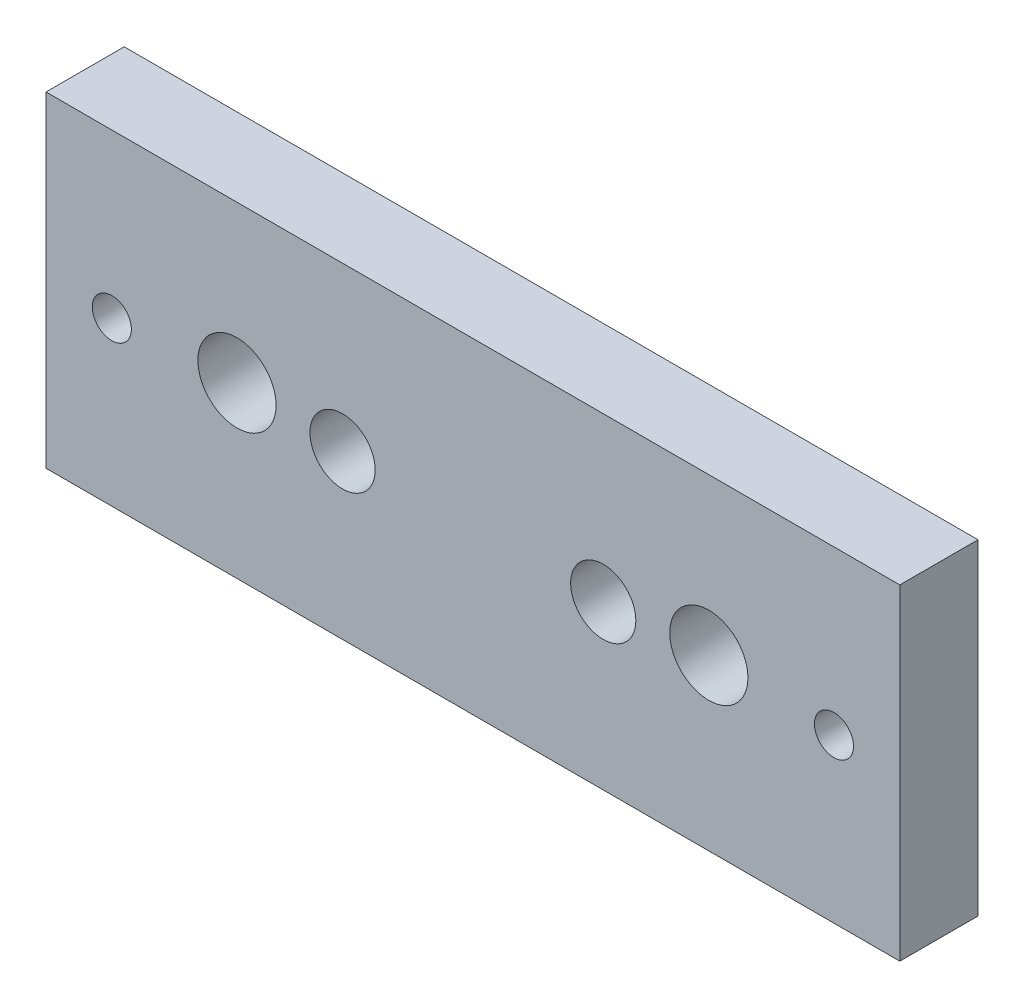
SolidWorks part; units mm, degrees
ref_plane "Płaszczyzna przednia" through (0, 0, 0) normal (0, 0, 1) x (1, 0, 0)
ref_plane "Płaszczyzna górna" through (0, 0, 0) normal (0, 1, 0) x (1, 0, 0)
ref_plane "Płaszczyzna prawa" through (0, 0, 0) normal (1, 0, 0) x (0, 0, -1)
sketch "Sketch1" plane through (0, 0, 0) normal (0, 0, 1) x (1, 0, 0)
  line L1 (0, 0) -> (65.5, 0)
  line L2 (0, 0) -> (0, 25)
  line L3 (0, 25) -> (65.5, 25)
  line L4 (65.5, 0) -> (65.5, 25)
  dimension "D1" = 65.5
  dimension "D2" = 25
extrude "Boss-Extrude1" add sketch "Sketch1" along normal blind 6
hole_wizard "Ø5.0mm Dowel Hole1" positions "Sketch2" profile "Sketch3" hole size "Ø5.0" standard "ANSI Metric" end condition through all
sketch "Sketch2" plane through (0, 0, 6) normal (0, 0, 1) x (1, 0, 0)
  line L0 (0, 0) -> (65.5, 0) construction
  line L1 (0, 25) -> (0, 0) construction
  point P0 (22.75, 12.5)
  point P2 (42.75, 12.5)
  dimension "D1" = 12.5
  dimension "D2" = 22.75
  dimension "D3" = 20
sketch "Sketch3" plane through (22.75, 12.5, 6) normal (1, 0, 0) x (0, -1, 0)
  line L0 (0, 0) -> (0, 6)
  line L1 (0, 6) -> (2.5, 6)
  line L2 (2.5, 6) -> (2.5, 0)
  line L5 (2.5, 0) -> (0, 0)
  line L11 (0, -6.35) -> (0, 107.95) construction
  dimension "Thru Hole Dia." = 5
  dimension "Thru Hole Depth" = 6
sketch "Sketch4" plane through (0, 0, 6) normal (0, 0, 1) x (1, 0, 0)
  line L0 (65.5, 25) -> (0, 25) construction
  line L1 (0, 25) -> (0, 0) construction
  circle A0 centre (14.65, 13) radius 3
  circle A1 centre (50.85, 13) radius 3
  point P4 (0, 0)
  point P5 (0, 0)
  dimension "D1" = 6
  dimension "D2" = 6
  dimension "D3" = 36.2
  dimension "D4" = 12
  dimension "D5" = 14.65
extrude "Cut-Extrude1" cut sketch "Sketch4" against normal through all
hole_wizard "Ø3.0mm Dowel Hole1" positions "Sketch5" profile "Sketch6" hole size "Ø3.0" standard "ANSI Metric" end condition through all
sketch "Sketch5" plane through (0, 0, 6) normal (0, 0, 1) x (1, 0, 0)
  line L0 (0, 25) -> (0, 0) construction
  line L1 (65.5, 25) -> (0, 25) construction
  line L2 (65.5, 0) -> (65.5, 25) construction
  point P0 (5.05, 12.5)
  point P2 (60.45, 12.5)
  point P5 (0, 0)
  dimension "D1" = 5.05
  dimension "D2" = 12.5
  dimension "D3" = 5.05
sketch "Sketch6" plane through (5.05, 12.5, 6) normal (1, 0, 0) x (0, -1, 0)
  line L0 (0, 0) -> (0, 6)
  line L1 (0, 6) -> (1.5, 6)
  line L2 (1.5, 6) -> (1.5, 0)
  line L5 (1.5, 0) -> (0, 0)
  line L11 (0, -6.35) -> (0, 107.95) construction
  dimension "Thru Hole Dia." = 3
  dimension "Thru Hole Depth" = 6
